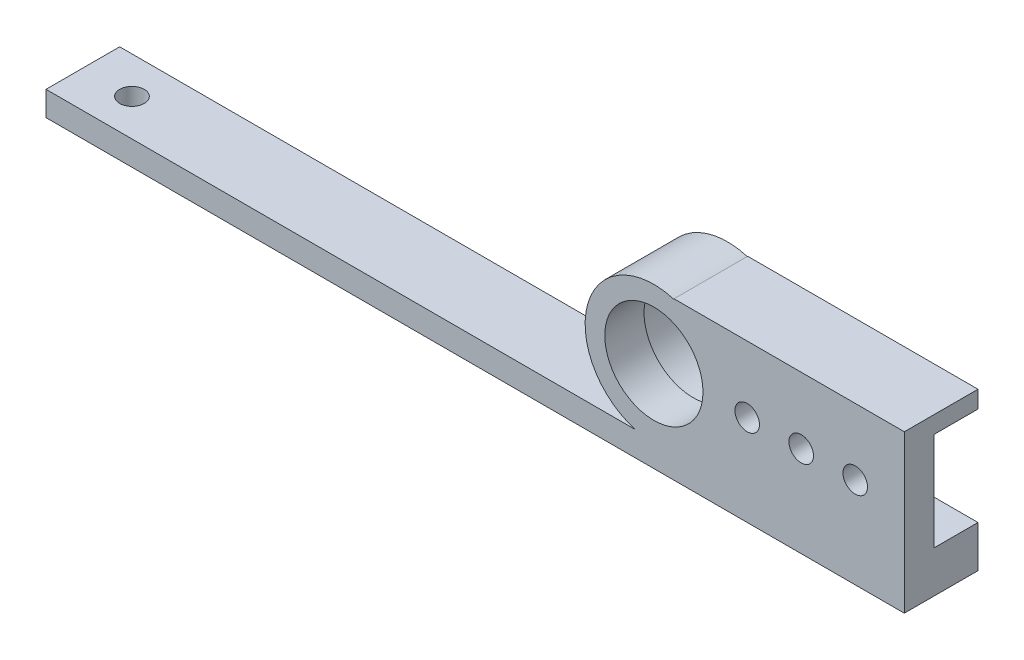
SolidWorks part; units mm, degrees
ref_plane "前视基准面" through (0, 0, 0) normal (0, 0, 1) x (1, 0, 0)
ref_plane "上视基准面" through (0, 0, 0) normal (0, 1, 0) x (1, 0, 0)
ref_plane "右视基准面" through (0, 0, 0) normal (1, 0, 0) x (0, 0, -1)
sketch "草图1" plane through (0, 0, 0) normal (0, 0, 1) x (1, 0, 0)
  line L1 (20, -10) -> (-20, -10)
  line L2 (20, -10) -> (20, 10)
  line L3 (20, 10) -> (-20, 10)
  line L4 (-20, -10) -> (-20, 10)
  line L5 (20, -10) -> (-20, 10) construction
  line L6 (20, 10) -> (-20, -10) construction
  point P0 (0, 0)
  dimension "D1" = 40
  dimension "D2" = 20
extrude "凸台-拉伸1" add sketch "草图1" along normal blind 6
sketch "草图2" plane through (0, 0, 6) normal (0, 0, 1) x (1, 0, 0)
  line L0 (20, -10) -> (20, 10) construction
  circle A0 centre (10, 0) radius 2.5
  circle A1 centre (-1, 0) radius 2.5
  circle A2 centre (-12, 0) radius 2.5
  dimension "D1" = 10
  dimension "D2" = 5
  dimension "D3" = 3
extrude "切除-拉伸1" cut sketch "草图2" against normal through all
sketch "草图3" plane through (0, 0, 6) normal (0, 0, 1) x (1, 0, 0)
  line L0 (20, 13.5) -> (20, 10)
  line L1 (20, -13.5) -> (-26.894, -13.5)
  line L3 (20, 13.5) -> (-26.894, 13.5)
  line L4 (-20, 10) -> (-20, -10)
  line L5 (-20, -10) -> (20, -10)
  line L6 (20, -10) -> (20, 10)
  line L7 (20, 10) -> (-20, 10)
  line L8 (-20, 10) -> (-20, -10)
  line L9 (-20, -10) -> (20, -10)
  line L10 (20, -10) -> (20, 10)
  line L11 (20, 10) -> (-20, 10)
  line L12 (-26.894, -13.5) -> (-26.894, 13.5)
  line L13 (20, -10.0394) -> (-26.894, 13.5) construction
  line L14 (20, 10.0394) -> (-26.894, -13.5) construction
  line L15 (20, -10) -> (20, -13.5)
  circle A0 centre (-31, 0) radius 11
  circle A1 centre (-31, 0) radius 14
  point P2 (0, 0)
  line M10 (-20, 10) -> (-20, -10)
  line M11 (-20, -10) -> (20, -10)
  line M13 (20, 10) -> (-20, 10)
  dimension "D3" = 22
  dimension "D4" = 28
  dimension "D2" = 3.5
  dimension "D1" = 0
extrude "凸台-拉伸2" add sketch "草图3" against normal blind 15 contours L3 A1 L1 L12 A0 | A1 L1 L15 M11 M10 | L1 A1 L8 A0 L12 | L8 A1 L3 L12 A0 | L8 A1 | A1 L0 L3 M10 M13 region at (-1.9449, 11.7771, 6) region at (-1.9449, -11.7771, 6) region at (-23.0173, 9.0328, 6) region at (-27.2274, 11.7946, 6) region at (-18.7882, 0, 6) region at (-23.0173, -9.0328, 6)
sketch "草图5" plane through (0, 0, 6) normal (0, 0, 1) x (1, 0, 0)
  circle A0 centre (-31, 0) radius 10
  circle A1 centre (-31, 0) radius 11 construction
  circle A2 centre (-31, 0) radius 11
  dimension "D1" = 20
extrude "凸台-拉伸3" add sketch "草图5" against normal blind 8
sketch "草图6" plane through (0, 0, 6) normal (0, 0, 1) x (1, 0, 0)
  circle A0 centre (-31, 0) radius 8.5
  circle A1 centre (-31, 0) radius 10 construction
  circle A2 centre (-31, 0) radius 10
  dimension "D1" = 17
sketch "草图9" plane through (0, -13.5, 0) normal (0, -1, 0) x (1, 0, 0)
  circle A0 centre (-18.2368, -1.344) radius 5.5352
sketch "草图10" plane through (20, 0, 0) normal (1, 0, 0) x (0, 0, -1)
  line L1 (9, -13.5) -> (-6, -13.5)
  line L2 (9, -13.5) -> (9, -18.5)
  line L3 (9, -18.5) -> (-6, -18.5)
  line L4 (-6, -13.5) -> (-6, -18.5)
  dimension "D1" = 5
extrude "凸台-拉伸4" add sketch "草图10" against normal blind 200
sketch "草图11" plane through (0, 0, 6) normal (0, 0, 1) x (1, 0, 0)
  line L1 (-28.6193, -11.8661) -> (-25.5243, -11.8661)
  line L2 (-28.6193, -11.8661) -> (-28.6193, -14.961)
  line L3 (-28.6193, -14.961) -> (-25.5243, -14.961)
  line L4 (-25.5243, -11.8661) -> (-25.5243, -14.961)
extrude "凸台-拉伸5" add sketch "草图11" against normal through all
sketch "草图13" plane through (0, -18.5, 0) normal (0, -1, 0) x (1, 0, 0)
  line L0 (-154.7729, 6) -> (-154.7729, -9)
  line L1 (-180, 6) -> (20, 6) construction
  line L2 (-154.7729, 124.91) -> (-154.7729, -245.09) construction
  line L3 (-180, -9) -> (20, -9) construction
sketch "草图14" plane through (0, -18.5, 0) normal (0, -1, 0) x (1, 0, 0)
  line L0 (-118.4338, -15.7251) -> (-118.4338, 9.3691)
  line L1 (-118.4338, 126.7017) -> (-118.4338, -243.2983) construction
sketch "草图15" plane through (0, -18.5, 0) normal (0, -1, 0) x (1, 0, 0)
  line L1 (-118.4338, -15.7251) -> (-184.1416, -15.7251)
  line L2 (-118.4338, -15.7251) -> (-118.4338, 11.9644)
  line L3 (-118.4338, 11.9644) -> (-184.1416, 11.9644)
  line L4 (-184.1416, -15.7251) -> (-184.1416, 11.9644)
sketch "草图16" plane through (0, -18.5, 0) normal (0, -1, 0) x (1, 0, 0)
  line L0 (-154.7729, 6.4407) -> (-154.7729, -38.9947)
  line L1 (-154.7729, 124.91) -> (-154.7729, -245.09) construction
sketch "草图17" plane through (0, -18.5, 0) normal (0, -1, 0) x (1, 0, 0)
  line L0 (-154.7729, 7.3332) -> (-154.7729, -35.3686)
  line L1 (-154.7729, 124.91) -> (-154.7729, -245.09) construction
sketch "草图18" plane through (0, -18.5, 0) normal (0, -1, 0) x (1, 0, 0)
  line L1 (-154.7729, -38.9947) -> (-206.846, -38.9947)
  line L2 (-154.7729, -38.9947) -> (-154.7729, 25.1925)
  line L3 (-154.7729, 25.1925) -> (-206.846, 25.1925)
  line L4 (-206.846, -38.9947) -> (-206.846, 25.1925)
extrude "切除-拉伸3" cut sketch "草图18" against normal through all
sketch "草图19" plane through (0, -18.5, 0) normal (0, -1, 0) x (1, 0, 0)
  line L0 (-154.7729, 6) -> (-154.7729, -9) construction
  line L1 (-154.7729, -1.5) -> (-144.7729, -1.5) construction
  circle A0 centre (-144.7729, -1.5) radius 2.5
  dimension "D1" = 5
  dimension "D2" = 10
extrude "切除-拉伸4" cut sketch "草图19" against normal through all
